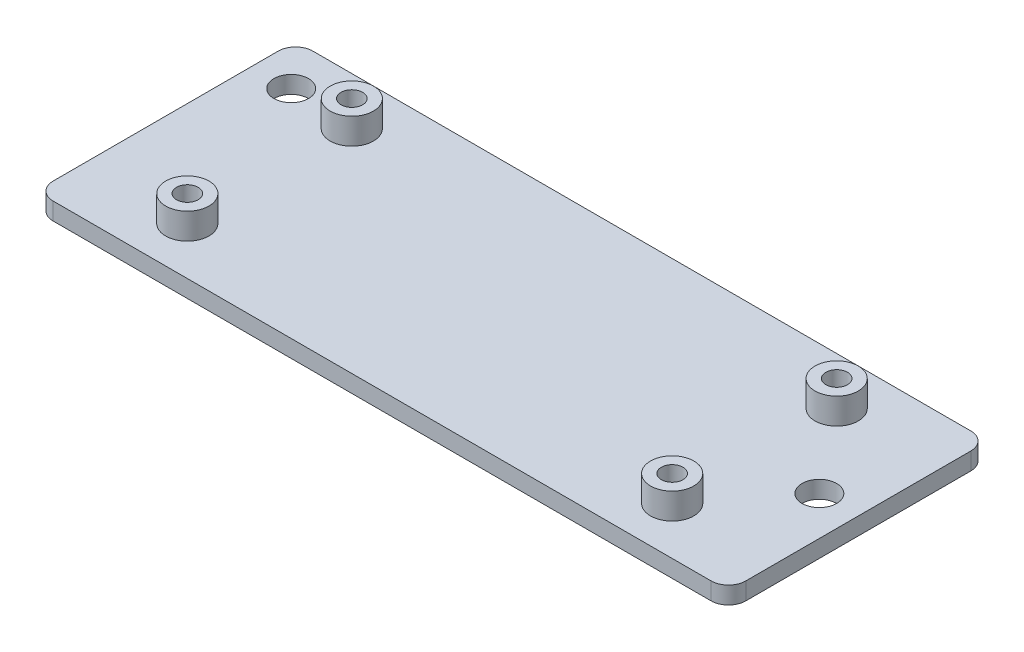
SolidWorks part; units mm, degrees
ref_plane "Спереди" through (0, 0, 0) normal (0, 0, 1) x (1, 0, 0)
ref_plane "Сверху" through (0, 0, 0) normal (0, 1, 0) x (1, 0, 0)
ref_plane "Справа" through (0, 0, 0) normal (1, 0, 0) x (0, 0, -1)
sketch "Эскиз1" plane through (0, 0, 0) normal (0, 1, 0) x (1, 0, 0)
  line L1 (0, 0) -> (80, 0)
  line L2 (0, 0) -> (0, -30)
  line L3 (0, -30) -> (80, -30)
  line L4 (80, 0) -> (80, -30)
  dimension "D1" = 30
  dimension "D2" = 80
extrude "Бобышка-Вытянуть1" add sketch "Эскиз1" along normal blind 2
sketch "Эскиз2" plane through (0, 2, 0) normal (0, 1, 0) x (1, 0, 0)
  line L0 (0, 0) -> (0, -30) construction
  line L1 (80, 0) -> (0, 0) construction
  line L3 (0, -30) -> (80, -30) construction
  line L4 (80, -30) -> (80, 0) construction
  circle A0 centre (12, -5.5) radius 2.5
  circle A1 centre (12, -24.5) radius 2.5
  circle A2 centre (68, -5.5) radius 2.5
  circle A3 centre (68, -24.5) radius 2.5
  dimension "D1" = 12
  dimension "D2" = 5.5
  dimension "D3" = 12
  dimension "D4" = 5.5
  dimension "D5" = 12
  dimension "D6" = 5.5
  dimension "D7" = 12
  dimension "D8" = 5.5
  dimension "D9" = 5
  dimension "D10" = 5
  dimension "D11" = 5
  dimension "D12" = 5
extrude "Бобышка-Вытянуть2" add sketch "Эскиз2" along normal blind 3
sketch "Эскиз3" plane through (0, 5, 0) normal (0, 1, 0) x (1, 0, 0)
  circle A0 centre (12, -5.5) radius 1.25
  circle A1 centre (12, -24.5) radius 1.25
  circle A2 centre (68, -5.5) radius 1.25
  circle A3 centre (68, -24.5) radius 1.25
  dimension "D1" = 2.5
  dimension "D2" = 2.5
  dimension "D3" = 2.5
  dimension "D4" = 2.5
extrude "Вырез-Вытянуть1" cut sketch "Эскиз3" against normal through all both and the other way through all
sketch "Эскиз4" plane through (0, 2, 0) normal (0, 1, 0) x (1, 0, 0)
  line L0 (0, -15) -> (80, -15) construction
  line L1 (0, 0) -> (0, -30) construction
  line L2 (80, -30) -> (80, 0) construction
  line L3 (80, 0) -> (0, 0) construction
  circle A0 centre (4.5, -5) radius 2
  circle A1 centre (75.5, -15) radius 2
  dimension "D1" = 4.5
  dimension "D2" = 4
  dimension "D3" = 4.5
  dimension "D4" = 4
  dimension "D5" = 5
extrude "Вырез-Вытянуть2" cut sketch "Эскиз4" against normal through all both and the other way through all
fillet "Скругление1" radius 2 1 edges at (0, 1, 30) type face fillet first side face at (0, 1, 15) second side face at (40, 1, 30)
fillet "Скругление2" radius 2 1 edges at (0, 1, 0) type face fillet first side face at (40, 1, 0) second side face at (0, 1, 14)
fillet "Скругление3" radius 2 1 edges at (80, 1, 0) type face fillet first side face at (41, 1, 0) second side face at (80, 1, 15)
fillet "Скругление4" radius 2 1 edges at (80, 1, 30) type face fillet first side face at (80, 1, 16) second side face at (41, 1, 30)
